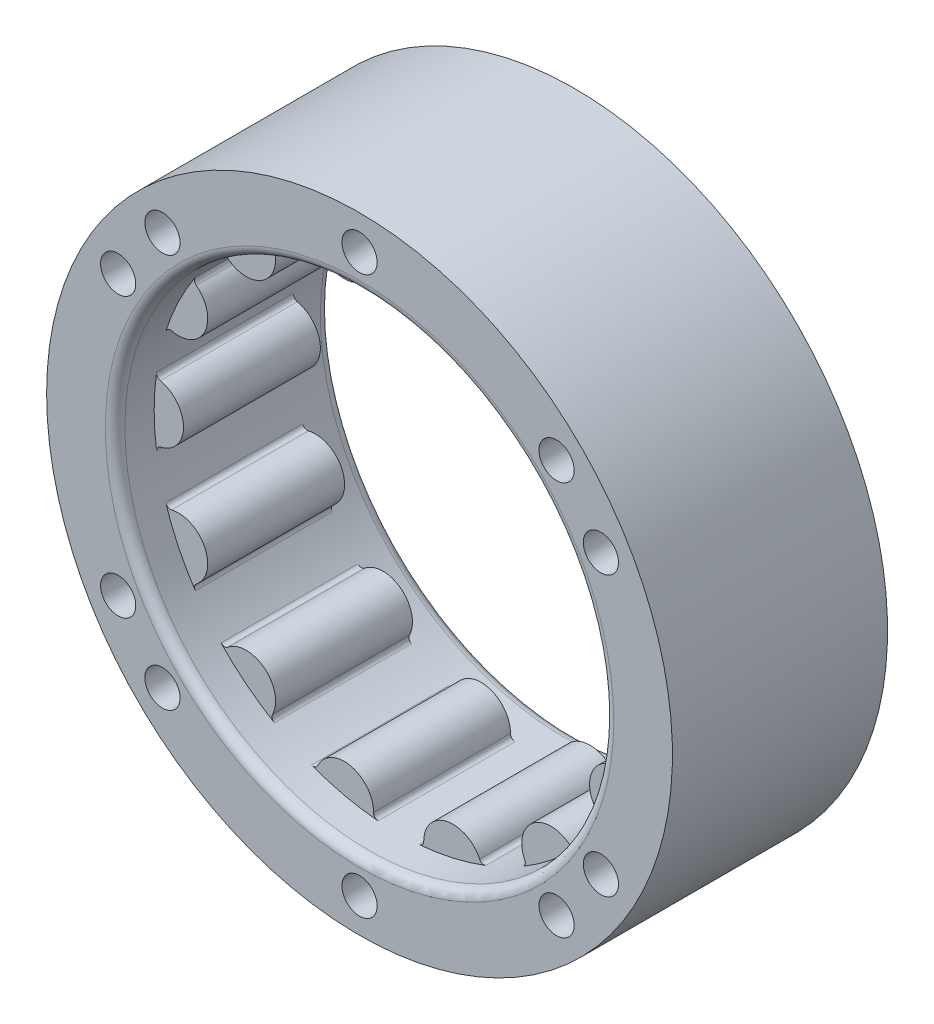
SolidWorks part; units mm, degrees
note: '?' marks a value the reader was unsure of.
ref_plane "前视基准面" through (0, 0, 0) normal (0, 0, 1) x (1, 0, 0)
ref_plane "上视基准面" through (0, 0, 0) normal (0, 1, 0) x (1, 0, 0)
ref_plane "右视基准面" through (0, 0, 0) normal (1, 0, 0) x (0, 0, -1)
other "Configuration Table"
ref_axis "基准轴1" through (0, 0, 55) along (0, 0, -1)?
sketch "PinsBaseSketch" plane through (0, 0, 0) normal (0, 0, 1) x (1, 0, 0)
  circle A0 centre (0, 0) radius 28
extrude "PinsBaseExtrude" add sketch "PinsBaseSketch" against normal blind 5 and the other way blind 0.4
sketch "PinsSketch" plane through (0, 0, 0) normal (0, 0, 1) x (1, 0, 0)
  circle A0 centre (25, 0) radius 3
  dimension "D1" = 6
extrude "PinsExtrude" add sketch "PinsSketch" along normal blind 8.4 and the other way blind 0.4
pattern_circular "PinsPattern" count 14 over 360 about axis through (0, 0, 0) along (0, 0, 1) of "PinsExtrude"
sketch "BoreRevolveSketch" plane through (0, 0, 0) normal (1, 0, 0) x (0, 0, -1)
  line L0 (0, 0) -> (1, 0) construction
  line L1 (-4, 0) -> (4, 0)
  line L2 (4, 0) -> (4, 5)
  line L3 (4, 5) -> (-4, 5)
  line L4 (-4, 5) -> (-4, 0)
  dimension "TaperSide1" = 5
  dimension "TaperSide2" = 5
revolve "BoreRevolveCut" cut sketch "BoreRevolveSketch" angle 360 about L0
sketch "草图1" plane through (0, 0, -4) normal (0, 0, 1) x (1, 0, 0)
  circle A1 centre (0, 0) radius 5
  circle A2 centre (0, 0) radius 5
  dimension "D1" = 0
extrude "切除-拉伸1" cut sketch "草图1" against normal through all
sketch "草图2" plane through (0, 0, 8.4) normal (0, 0, 1) x (1, 0, 0)
  circle A0 centre (-5.563, -24.3732) radius 3 construction
  circle A1 centre (-15.5872, -19.5458) radius 3
  circle A2 centre (-15.5872, -19.5458) radius 3
  circle A3 centre (5.563, -24.3732) radius 3 construction
  circle A4 centre (15.5872, -19.5458) radius 3 construction
  circle A5 centre (22.5242, -10.8471) radius 3 construction
  circle A6 centre (25, 0) radius 3 construction
  circle A7 centre (22.5242, 10.8471) radius 3 construction
  circle A8 centre (15.5872, 19.5458) radius 3 construction
  circle A9 centre (5.563, 24.3732) radius 3 construction
  circle A10 centre (-5.563, 24.3732) radius 3 construction
  circle A11 centre (-15.5872, 19.5458) radius 3 construction
  circle A12 centre (-25, 0) radius 3 construction
  circle A13 centre (-22.5242, 10.8471) radius 3 construction
  circle A14 centre (-22.5242, -10.8471) radius 3 construction
  circle A15 centre (-5.563, -24.3732) radius 3
  circle A16 centre (5.563, -24.3732) radius 3
  circle A17 centre (15.5872, -19.5458) radius 3
  circle A18 centre (22.5242, -10.8471) radius 3
  circle A19 centre (25, 0) radius 3
  circle A20 centre (22.5242, 10.8471) radius 3
  circle A21 centre (15.5872, 19.5458) radius 3
  circle A22 centre (5.563, 24.3732) radius 3
  circle A23 centre (-5.563, 24.3732) radius 3
  circle A24 centre (-15.5872, 19.5458) radius 3
  circle A25 centre (-25, 0) radius 3
  circle A26 centre (-22.5242, 10.8471) radius 3
  circle A27 centre (-22.5242, -10.8471) radius 3
  dimension "D1" = 0
extrude "凸台-拉伸1" add sketch "草图2" along normal blind 12
sketch "草图3" plane through (0, 0, -5) normal (0, 0, -1) x (-1, 0, 0)
  circle A0 centre (0, 0) radius 5 construction
  circle A1 centre (0, 0) radius 28
  circle A2 centre (0, 0) radius 28
  circle A3 centre (0, 0) radius 5
  dimension "D1" = 0
extrude "切除-拉伸2" cut sketch "草图3" against normal blind 0.4 contours A2 | A3
sketch "草图5" plane through (0, 0, 0.4) normal (0, 0, 1) x (1, 0, 0)
  circle A0 centre (0, 0) radius 25
  dimension "D1" = 50
extrude "切除-拉伸3" cut sketch "草图5" against normal through all
sketch "草图7" plane through (0, 0, -4.6) normal (0, 0, -1) x (-1, 0, 0)
  circle A0 centre (0, 0) radius 29
  circle A1 centre (0, 0) radius 28 construction
  circle A2 centre (0, 0) radius 28
  dimension "D1" = 58
extrude "凸台-拉伸2" add sketch "草图7" against normal blind 5
sketch "草图17" plane through (0, 0, 0.4) normal (0, 0, 1) x (1, 0, 0)
  arc A0 (-17.8163, 17.538) -> (-21.0627, 13.467) centre (0, 0) ccw construction
  circle A1 centre (-22.5242, 10.8471) radius 3
  circle A2 centre (-22.5242, 10.8471) radius 3
  arc A3 (-17.8163, 17.538) -> (-21.0627, 13.467) centre (0, 0) ccw
  circle A4 centre (-15.5872, 19.5458) radius 3
  arc A5 (-8.4425, 23.5314) -> (-13.1337, 21.2722) centre (0, 0) ccw
  circle A6 centre (-5.563, 24.3732) radius 3
  arc A7 (2.6035, 24.8641) -> (-2.6035, 24.8641) centre (0, 0) ccw
  circle A8 centre (5.563, 24.3732) radius 3
  arc A9 (13.1337, 21.2722) -> (8.4425, 23.5314) centre (0, 0) ccw
  circle A10 centre (15.5872, 19.5458) radius 3
  arc A11 (21.0627, 13.467) -> (17.8163, 17.538) centre (0, 0) ccw
  circle A12 centre (22.5242, 10.8471) radius 3
  arc A13 (24.82, 2.9946) -> (23.6614, 8.071) centre (0, 0) ccw
  circle A14 centre (25, 0) radius 3
  arc A15 (23.6614, -8.071) -> (24.82, -2.9946) centre (0, 0) ccw
  circle A16 centre (22.5242, -10.8471) radius 3
  arc A17 (17.8163, -17.538) -> (21.0627, -13.467) centre (0, 0) ccw
  circle A18 centre (15.5872, -19.5458) radius 3
  arc A19 (8.4425, -23.5314) -> (13.1337, -21.2722) centre (0, 0) ccw
  circle A20 centre (5.563, -24.3732) radius 3
  arc A21 (-2.6035, -24.8641) -> (2.6035, -24.8641) centre (0, 0) ccw
  circle A22 centre (-5.563, -24.3732) radius 3
  arc A23 (-13.1337, -21.2722) -> (-8.4425, -23.5314) centre (0, 0) ccw
  circle A24 centre (-15.5872, -19.5458) radius 3
  arc A25 (-21.0627, -13.467) -> (-17.8163, -17.538) centre (0, 0) ccw
  circle A26 centre (-22.5242, -10.8471) radius 3
  arc A27 (-24.82, -2.9946) -> (-23.6614, -8.071) centre (0, 0) ccw
  circle A28 centre (-25, 0) radius 3
  arc A29 (-23.6614, 8.071) -> (-24.82, 2.9946) centre (0, 0) ccw
  circle A30 centre (0, 0) radius 29 construction
  circle A31 centre (0, 0) radius 29
  point P60 (0, 0)
  arc M2 (24.82, -2.9946) -> (23.6614, -8.071) centre (0, 0) cw
  arc M3 (23.6614, -8.071) -> (21.0627, -13.467) centre (22.5242, -10.8471) cw
  arc M4 (21.0627, -13.467) -> (17.8163, -17.538) centre (0, 0) cw
  arc M5 (17.8163, -17.538) -> (13.1337, -21.2722) centre (15.5872, -19.5458) cw
  arc M6 (13.1337, -21.2722) -> (8.4425, -23.5314) centre (0, 0) cw
  arc M7 (8.4425, -23.5314) -> (2.6035, -24.8641) centre (5.563, -24.3732) cw
  arc M8 (2.6035, -24.8641) -> (-2.6035, -24.8641) centre (0, 0) cw
  arc M9 (-2.6035, -24.8641) -> (-8.4425, -23.5314) centre (-5.563, -24.3732) cw
  arc M10 (-8.4425, -23.5314) -> (-13.1337, -21.2722) centre (0, 0) cw
  arc M11 (-13.1337, -21.2722) -> (-17.8163, -17.538) centre (-15.5872, -19.5458) cw
  arc M12 (-17.8163, -17.538) -> (-21.0627, -13.467) centre (0, 0) cw
  arc M13 (-21.0627, -13.467) -> (-23.6614, -8.071) centre (-22.5242, -10.8471) cw
  arc M14 (-23.6614, -8.071) -> (-24.82, -2.9946) centre (0, 0) cw
  arc M15 (-24.82, -2.9946) -> (-24.82, 2.9946) centre (-25, 0) cw
  arc M16 (-24.82, 2.9946) -> (-23.6614, 8.071) centre (0, 0) cw
  arc M17 (-23.6614, 8.071) -> (-21.0627, 13.467) centre (-22.5242, 10.8471) cw
  arc M18 (-21.0627, 13.467) -> (-17.8163, 17.538) centre (0, 0) cw
  arc M19 (-17.8163, 17.538) -> (-13.1337, 21.2722) centre (-15.5872, 19.5458) cw
  arc M20 (-13.1337, 21.2722) -> (-8.4425, 23.5314) centre (0, 0) cw
  arc M21 (-8.4425, 23.5314) -> (-2.6035, 24.8641) centre (-5.563, 24.3732) cw
  arc M22 (-2.6035, 24.8641) -> (2.6035, 24.8641) centre (0, 0) cw
  arc M23 (2.6035, 24.8641) -> (8.4425, 23.5314) centre (5.563, 24.3732) cw
  arc M24 (8.4425, 23.5314) -> (13.1337, 21.2722) centre (0, 0) cw
  arc M25 (13.1337, 21.2722) -> (17.8163, 17.538) centre (15.5872, 19.5458) cw
  arc M26 (17.8163, 17.538) -> (21.0627, 13.467) centre (0, 0) cw
  arc M27 (21.0627, 13.467) -> (23.6614, 8.071) centre (22.5242, 10.8471) cw
  arc M28 (23.6614, 8.071) -> (24.82, 2.9946) centre (0, 0) cw
  arc M29 (24.82, 2.9946) -> (24.82, -2.9946) centre (25, 0) cw
  circle M30 centre (0, 0) radius 29
  dimension "D1" = 0
  dimension "D2" = 14
extrude "凸台-拉伸9" add sketch "草图17" along normal blind 20 contours M30 M29 M2 M3 M4 M5 M6 M7 M8 M9 M10 M11 M12 M13 M14 M15 M16 M17 M18 M19 M20 M21 M22 M23 M24 M25 M26 M27 M28
sketch "草图18" plane through (0, 0, -4.6) normal (0, 0, -1) x (-1, 0, 0)
  circle A1 centre (0, 0) radius 29
  circle A2 centre (0, 0) radius 29
  dimension "D1" = 0
extrude "切除-拉伸5" cut sketch "草图18" against normal blind 5
fillet "圆角1" radius 0.5 28 edges at (24.82, 2.9946, 10.4) (24.82, -2.9946, 10.4) (23.6614, -8.071, 10.4) (21.0627, -13.467, 10.4) (17.8163, -17.538, 10.4) (13.1337, -21.2722, 10.4) (8.4425, -23.5314, 10.4) (2.6035, -24.8641, 10.4) (-2.6035, -24.8641, 10.4) (-8.4425, -23.5314, 10.4) (-13.1337, -21.2722, 10.4) (-17.8163, -17.538, 10.4) (-21.0627, -13.467, 10.4) (-23.6614, -8.071, 10.4) (-24.82, -2.9946, 10.4) (-24.82, 2.9946, 10.4) (-23.6614, 8.071, 10.4) (-21.0627, 13.467, 10.4) (-17.8163, 17.538, 10.4) (-13.1337, 21.2722, 10.4) (-8.4425, 23.5314, 10.4) (-2.6035, 24.8641, 10.4) (2.6035, 24.8641, 10.4) (8.4425, 23.5314, 10.4) (13.1337, 21.2722, 10.4) (17.8163, 17.538, 10.4) (21.0627, 13.467, 10.4) (23.6614, 8.071, 10.4)
sketch "草图20" plane through (0, 0, 0.4) normal (0, 0, -1) x (-1, 0, 0)
  circle A0 centre (0, 0) radius 29
  circle A1 centre (0, 0) radius 29 construction
extrude "切除-拉伸7" cut sketch "草图20" against normal blind 6
sketch "草图21" plane through (0, 0, 20.4) normal (0, 0, 1) x (1, 0, 0)
  circle A0 centre (0, 0) radius 29
  circle A1 centre (0, 0) radius 29 construction
  circle A2 centre (0, 0) radius 25
  dimension "D1" = 50
extrude "凸台-拉伸10" add sketch "草图21" along normal blind 4
sketch "草图22" plane through (0, 0, 6.4) normal (0, 0, -1) x (-1, 0, 0)
  circle A0 centre (0, 0) radius 29
  circle A1 centre (0, 0) radius 25
  dimension "D1" = 50
extrude "凸台-拉伸11" add sketch "草图22" along normal blind 4
sketch "草图23" plane through (0, 0, 2.4) normal (0, 0, -1) x (-1, 0, 0)
  circle A0 centre (0, 0) radius 29
  circle A1 centre (0, 0) radius 32
  dimension "D1" = 64
extrude "凸台-拉伸12" add sketch "草图23" against normal blind 22
sketch "草图24" plane through (0, 0, 2.4) normal (0, 0, -1) x (-1, 0, 0)
  circle A1 centre (0, 0) radius 28.5 construction
  circle A2 centre (0, 28.5) radius 1.8
  circle A3 centre (24.6817, 14.25) radius 1.8
  circle A4 centre (24.6817, -14.25) radius 1.8
  circle A5 centre (0, -28.5) radius 1.8
  circle A6 centre (-24.6817, -14.25) radius 1.8
  circle A7 centre (-24.6817, 14.25) radius 1.8
  point P18 (0, 0)
  dimension "D1" = 57
  dimension "D2" = 3.6
  dimension "D3" = 6
extrude "切除-拉伸8" cut sketch "草图24" against normal through all
sketch "草图25" plane through (0, 0, 24.4) normal (0, 0, 1) x (1, 0, 0)
  circle A0 centre (20.1525, 20.1525) radius 1.8
  circle A1 centre (20.1525, -20.1525) radius 1.8
  circle A2 centre (-20.1525, -20.1525) radius 1.8
  circle A3 centre (-20.1525, 20.1525) radius 1.8
  point P12 (0, 0)
  dimension "D1" = 3.6
  dimension "D2" = 4
extrude "切除-拉伸9" cut sketch "草图25" against normal blind 5
fillet "圆角2" radius 1 2 edges at (25, 0, 24.4) (-25, 0, 2.4)
